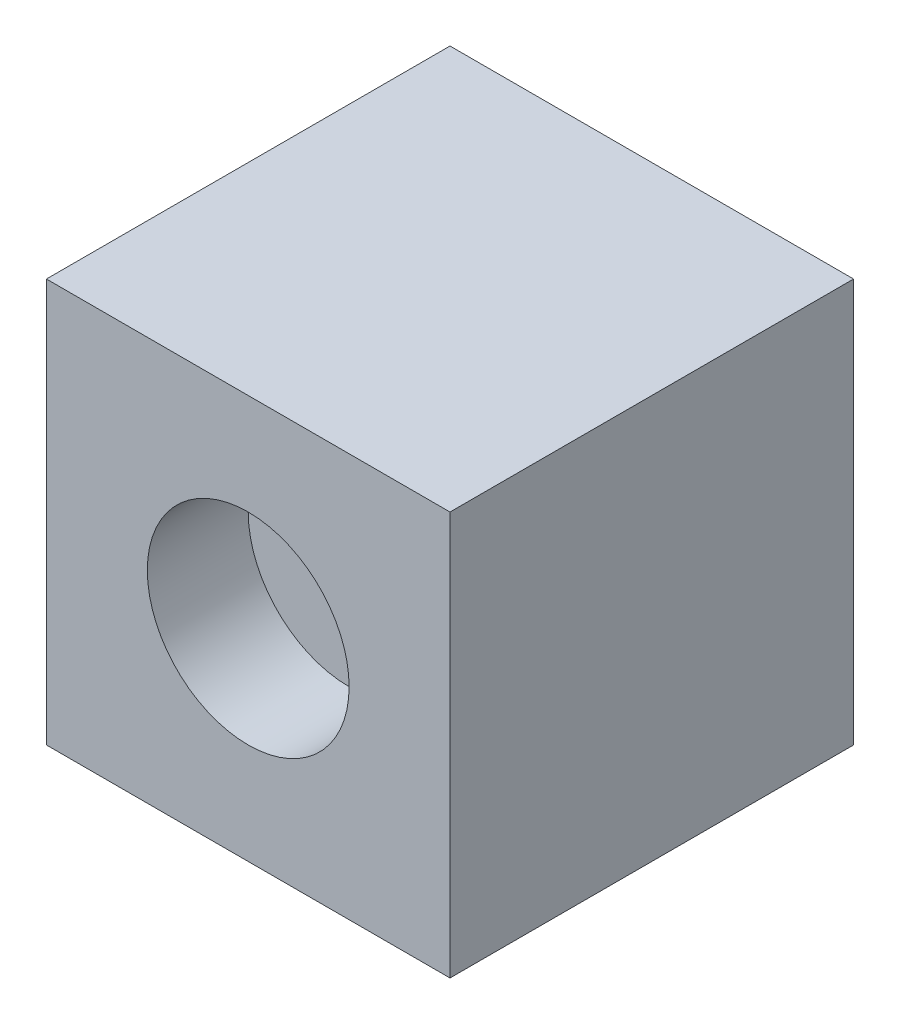
SolidWorks part; units mm, degrees
ref_plane "Front Plane" through (0, 0, 0) normal (0, 0, 1) x (1, 0, 0)
ref_plane "Top Plane" through (0, 0, 0) normal (0, 1, 0) x (1, 0, 0)
ref_plane "Right Plane" through (0, 0, 0) normal (1, 0, 0) x (0, 0, -1)
sketch "Sketch1" plane through (0, 0, 0) normal (0, 0, 1) x (1, 0, 0)
  line L1 (-10, 10) -> (10, 10)
  line L2 (-10, 10) -> (-10, -10)
  line L3 (-10, -10) -> (10, -10)
  line L4 (10, 10) -> (10, -10)
  line L5 (-10, 10) -> (10, -10) construction
  line L6 (-10, -10) -> (10, 10) construction
  point P0 (0, 0)
  dimension "D1" = 20
  dimension "D2" = 20
extrude "Boss-Extrude1" add sketch "Sketch1" along normal blind 20
sketch "Sketch2" plane through (0, 0, 20) normal (0, 0, 1) x (1, 0, 0)
  circle A0 centre (0, 0) radius 5
  dimension "D1" = 10
extrude "Cut-Extrude1" cut sketch "Sketch2" against normal blind 5
